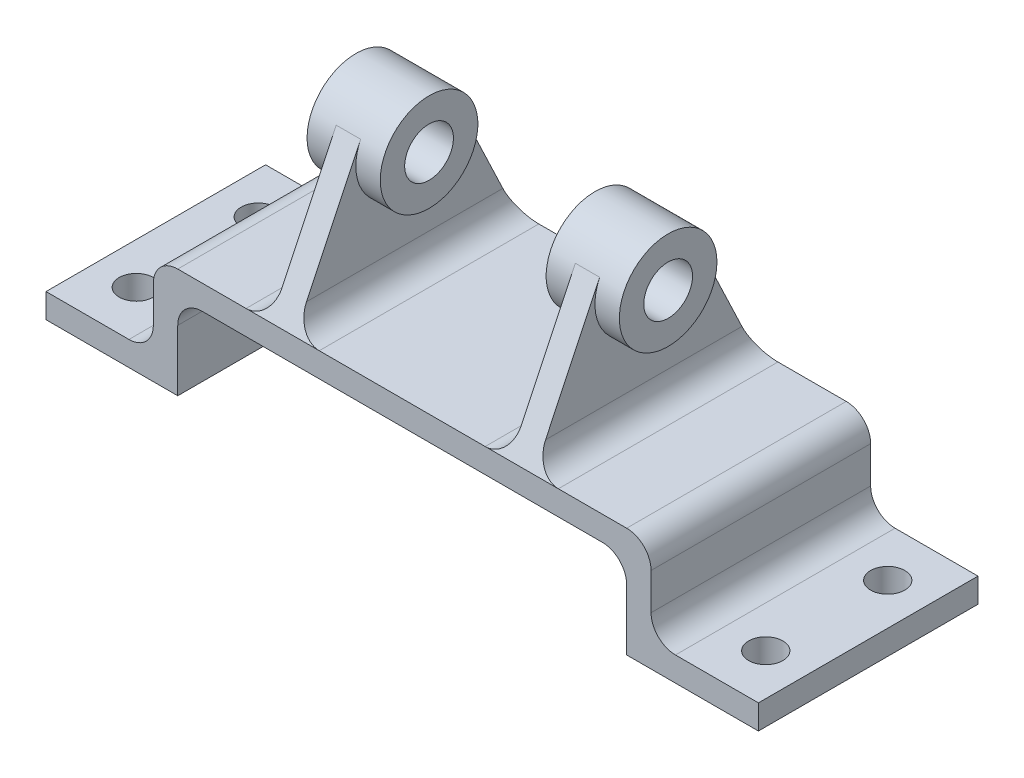
SolidWorks part; units mm, degrees
ref_plane "Front Plane" through (0, 0, 0) normal (0, 0, 1) x (1, 0, 0)
ref_plane "Top Plane" through (0, 0, 0) normal (0, 1, 0) x (1, 0, 0)
ref_plane "Right Plane" through (0, 0, 0) normal (1, 0, 0) x (0, 0, -1)
sketch "Sketch1" plane through (0, 0, 0) normal (0, 0, 1) x (1, 0, 0)
  line L0 (-102, 10) -> (102, 10)
  line L2 (92, 0) -> (-92, 0)
  line L3 (-102, 10) -> (-102, -25)
  line L4 (-102, -25) -> (-146, -25)
  line L5 (-92, 0) -> (-92, -35)
  line L8 (92, 0) -> (92, -35)
  line L9 (102, 10) -> (102, -25)
  line L10 (-92, -35) -> (-146, -35)
  line L11 (-146, -35) -> (-146, -25)
  line L12 (102, -25) -> (146, -25)
  line L13 (146, -25) -> (146, -35)
  line L14 (146, -35) -> (92, -35)
  dimension "D1" = 92
  dimension "D2" = 102
  dimension "D3" = 146
  dimension "D4" = 92
  dimension "D5" = 10
  dimension "D6" = 25
extrude "Boss-Extrude1" add sketch "Sketch1" against normal blind 90
fillet "Fillet1" radius 10 4 edges at (102, 10, -45) (-102, 10, -45) (-102, -25, -45) (102, -25, -45)
sketch "Sketch2" plane through (0, -25, 0) normal (0, 1, 0) x (1, 0, 0)
  line L0 (112, 90) -> (112, 0) construction
  line L1 (146, 90) -> (112, 90) construction
  circle A0 centre (129, 20) radius 7
  circle A1 centre (129, 70) radius 7
  circle A2 centre (-129, 70) radius 7
  circle A3 centre (-129, 20) radius 7
  dimension "D1" = 14
  dimension "D2" = 17
  dimension "D3" = 241
  dimension "D4" = 20
  dimension "D5" = 70
extrude "Cut-Extrude1" cut sketch "Sketch2" against normal blind 10
sketch "Sketch10" plane through (-102, 0, 0) normal (-1, 0, 0) x (0, 0, 1)
  line L0 (0, 0) -> (0, -15) construction
  line L1 (0, 0) -> (-90, 0) construction
  circle A0 centre (-45, 48) radius 10
  circle A1 centre (-45, 48) radius 20
  dimension "D1" = 20
  dimension "D2" = 40
  dimension "D3" = 45
  dimension "D4" = 48
extrude "Boss-Extrude5" add sketch "Sketch10" against normal blind 68 separate body
sketch "Sketch11" plane through (-102, 0, 0) normal (-1, 0, 0) x (0, 0, 1)
  circle A0 centre (-45, 48) radius 10 construction
  circle A1 centre (-45, 48) radius 20 construction
  circle A2 centre (-45, 48) radius 10
  circle A3 centre (-45, 48) radius 20
extrude "Cut-Extrude5" cut sketch "Sketch11" against normal blind 38
ref_plane "Plane1" through (-49, 0, 0) normal (1, 0, 0) x (0, 0, -1)
move or copy body "Body-Move/Copy1" bodies to move or copy 113 copy no translate (0, 10, 0)
sketch "Sketch14" plane through (-49, 0, 0) normal (1, 0, 0) x (0, 0, -1)
  line L2 (0, 10) -> (90, 10) construction
  line L3 (45, 10) -> (0, 10)
  line L4 (0, 62.15) -> (0, -62.15) construction
  line L5 (26.9417, 66.5963) -> (0, 10)
  line L6 (45, 10) -> (90, 10)
  line L7 (90, 10) -> (63.0583, 66.5963)
  arc A0 (26.9417, 66.5963) -> (63.0583, 66.5963) centre (45, 58) ccw
  dimension "D1" = 20
extrude "Boss-Extrude6" add sketch "Sketch14" along normal blind 5 and the other way blind 5
fillet "Fillet3" radius 10 2 edges at (-44, 10, -45) (-54, 10, -45)
sketch "Sketch15" plane through (102, 0, 0) normal (1, 0, 0) x (0, 0, -1)
  circle A0 centre (45, 58) radius 10
  circle A1 centre (45, 58) radius 20
  dimension "D1" = 20
  dimension "D2" = 40
extrude "Boss-Extrude7" add sketch "Sketch15" against normal blind 68 separate body
sketch "Sketch16" plane through (102, 0, 0) normal (1, 0, 0) x (0, 0, -1)
  circle A0 centre (45, 58) radius 10 construction
  circle A1 centre (45, 58) radius 20 construction
  circle A2 centre (45, 58) radius 10
  circle A3 centre (45, 58) radius 20
extrude "Cut-Extrude6" cut sketch "Sketch16" against normal blind 38
ref_plane "Plane2" through (49, 0, 0) normal (1, 0, 0) x (0, 0, -1)
sketch "Sketch17" plane through (49, 0, 0) normal (1, 0, 0) x (0, 0, -1)
  line L1 (45, 10) -> (0, 10)
  line L2 (0, 10) -> (26.9417, 66.5963)
  line L3 (45, 10) -> (90, 10)
  line L4 (90, 10) -> (63.0583, 66.5963)
  arc A0 (26.9417, 66.5963) -> (63.0583, 66.5963) centre (45, 58) ccw
  dimension "D1" = 20
  dimension "D2" = 26.9417
extrude "Boss-Extrude8" add sketch "Sketch17" along normal blind 5 and the other way blind 5
fillet "Fillet4" radius 10 4 edges at (44, 10, -45) (54, 10, -45) (-92, 0, -45) (92, 0, -45)
